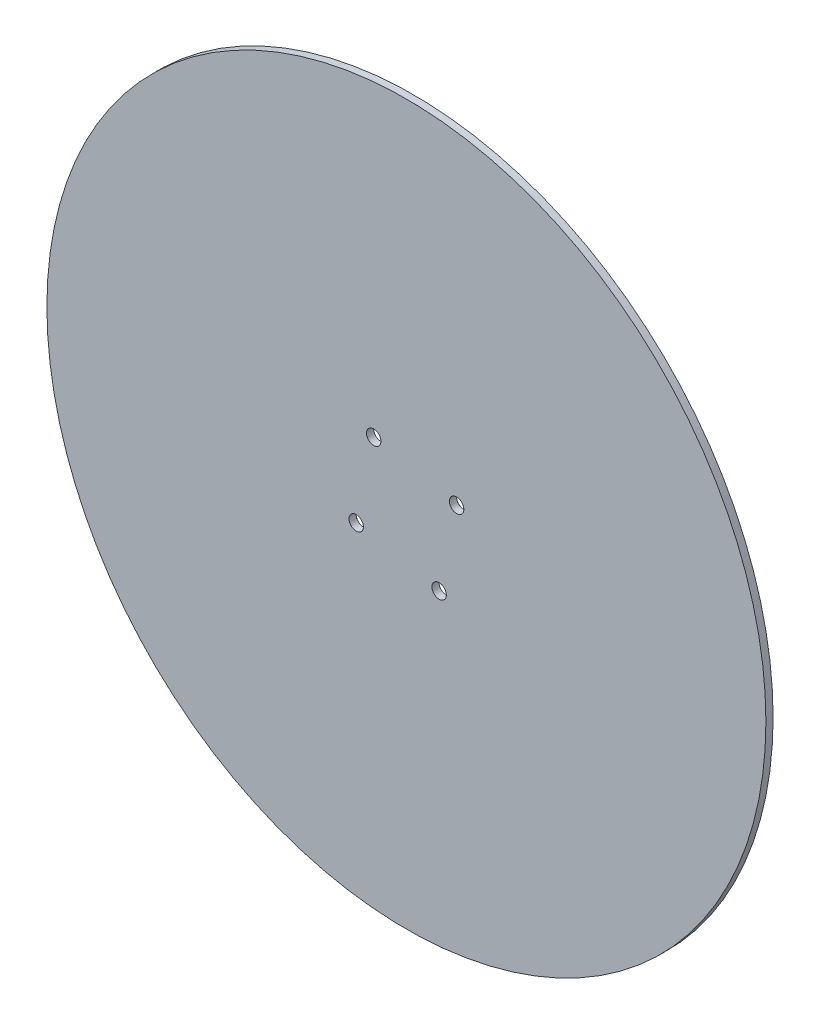
SolidWorks part; units mm, degrees
ref_plane "Front Plane" through (0, 0, 0) normal (0, 0, 1) x (1, 0, 0)
ref_plane "Top Plane" through (0, 0, 0) normal (0, 1, 0) x (1, 0, 0)
ref_plane "Right Plane" through (0, 0, 0) normal (1, 0, 0) x (0, 0, -1)
sketch "Sketch1" plane through (0, 0, 0) normal (0, 0, 1) x (1, 0, 0)
  line L0 (0, 0) -> (0, 140) construction
  line L1 (0, 140) -> (0, 150) construction
  line L2 (-12.5, 140) -> (12.5, 140) construction
  circle A0 centre (0, 0) radius 150
  point P9 (0, 140)
  point P21 (0, 0)
  dimension "D1" = 300
  dimension "D5" = 140
extrude "Boss-Extrude2" add sketch "Sketch1" along normal blind 3
sketch "Sketch2" plane through (0, 0, 0) normal (0, 0, -1) x (-1, 0, 0)
  circle A13 centre (-13.6439, -20.9486) radius 3.2 construction
  circle A14 centre (20.9486, -13.6439) radius 3.2 construction
  circle A15 centre (13.6439, 20.9486) radius 3.2 construction
  circle A16 centre (-20.9486, 13.6439) radius 3.2 construction
  circle A17 centre (-13.6439, -20.9486) radius 3.2
  circle A18 centre (20.9486, -13.6439) radius 3.2
  circle A19 centre (13.6439, 20.9486) radius 3.2
  circle A20 centre (-20.9486, 13.6439) radius 3.2
hole_wizard "Ø6.0mm Dowel Hole1" positions "Sketch8" profile "Sketch9" hole size "Ø6.0" standard "ANSI Metric" end condition through all
sketch "Sketch8" plane through (0, 0, 0) normal (0, 0, -1) x (-1, 0, 0)
  point P0 (-20.9486, 13.6439)
  point P3 (13.6439, 20.9486)
  point P6 (20.9486, -13.6439)
  point P9 (-13.6439, -20.9486)
sketch "Sketch9" plane through (20.9486, 13.6439, 0) normal (1, 0, 0) x (0, 1, 0)
  line L0 (0, 0) -> (0, 3)
  line L1 (0, 3) -> (3, 3)
  line L2 (3, 3) -> (3, 0.025)
  line L3 (3, 0.025) -> (3.025, 0)
  line L5 (3.025, 0) -> (0, 0)
  line L6 (-3, 0.025) -> (-3.025, 0) construction
  line L11 (0, -6.35) -> (0, 107.95) construction
  dimension "Thru Hole Dia." = 6
  dimension "Thru Hole Depth" = 3
  dimension "Near C'Sink Dia." = 6.05
  dimension "Near C'Sink Angle" = 90
